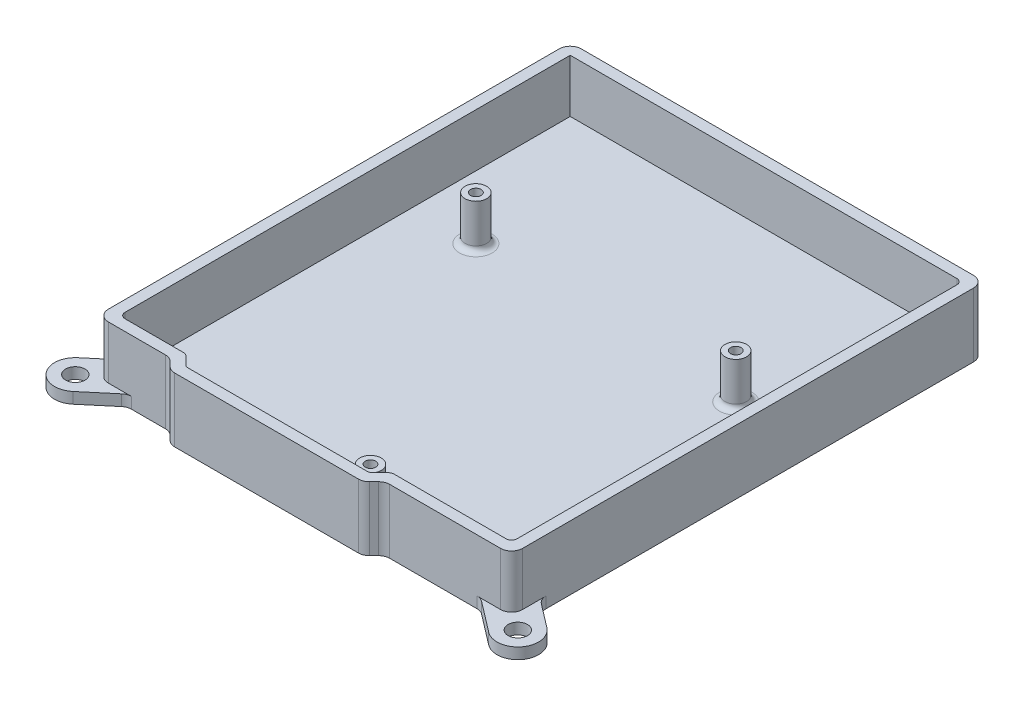
SolidWorks part; units mm, degrees
ref_plane "Alzado" through (0, 0, 0) normal (0, 0, 1) x (1, 0, 0)
ref_plane "Planta" through (0, 0, 0) normal (0, 1, 0) x (1, 0, 0)
ref_plane "Vista lateral" through (0, 0, 0) normal (1, 0, 0) x (0, 0, -1)
sketch "Croquis1" plane through (0, 0, 0) normal (0, 1, 0) x (1, 0, 0)
  line B0 (-18.7249, 81.5) -> (70.898, 81.5)
  line B1 (70.898, 81.5) -> (70.898, 0)
  line B2 (70.898, 0) -> (49.2071, 0)
  line B3 (49.2071, 0) -> (47.2071, -2)
  line B4 (47.2071, -2) -> (14, -2)
  line B5 (14, -2) -> (12, 0)
  line B6 (12, 0) -> (0, 0)
  line B7 (0, 0) -> (0, 55.5)
  line B8 (0, 55.5) -> (-18.7249, 55.5)
  line B9 (-18.7249, 55.5) -> (-18.7249, 81.5)
  circle B10 centre (-16.2249, 78.75) radius 0.95
  circle B11 centre (-16.2249, 58.25) radius 0.95
  circle B12 centre (11.37, 53.07) radius 0.95
  circle B13 centre (59.63, 51.8) radius 0.95
  circle B14 centre (44.39, 1) radius 0.95
  circle B15 centre (75.675, -3.65) radius 1.75
  circle B16 centre (75.675, 86.35) radius 1.75
  circle B17 centre (-24.325, 86.35) radius 1.75
  circle B18 centre (-4.325, -3.65) radius 1.75
sketch_block_instance "Bloque1-1"
sketch_block "Bloque1"
sketch "Croquis2" plane through (0, 0, 0) normal (0, 1, 0) x (1, 0, 0)
  line L0 (-2, -0.7077) -> (-2, 3.2191) construction
  line L1 (-2, 3.2191) -> (-2, 53.5)
  line L2 (-2, -2) -> (-2, 53.5) construction
  line L3 (-2, -1.6879) -> (-2, -0.7077) construction
  line L4 (-2.9876, -2.5213) -> (-2, -1.6879) construction
  line L5 (0, 55.5) -> (0, 83.5)
  line L6 (-2, 53.5) -> (-2, 83.5)
  line L7 (0, 55.5) -> (-18.7249, 55.5) construction
  line L8 (-18.7249, 81.5) -> (70.898, 81.5) construction
  line L16 (70.898, 81.5) -> (70.898, 0) construction
  line L17 (70.898, 0) -> (49.2071, 0) construction
  line L18 (49.2071, 0) -> (47.2071, -2) construction
  line L19 (47.2071, -2) -> (14, -2) construction
  line L20 (14, -2) -> (12, 0) construction
  line L21 (12, 0) -> (0, 0) construction
  line L22 (0, 0) -> (0, 55.5) construction
  line L24 (-18.7249, 81.5) -> (70.898, 81.5) construction
  line L26 (70.898, 81.5) -> (70.898, 0) construction
  line L27 (70.898, 0) -> (49.2071, 0) construction
  line L28 (49.2071, 0) -> (47.2071, -2)
  line L29 (47.2071, -2) -> (14, -2)
  line L30 (14, -2) -> (12, 0)
  line L31 (12, 0) -> (0, 0) construction
  line L32 (0, 0) -> (0, 55.5)
  line L34 (-2, 81.5) -> (70.898, 81.5) construction
  line L36 (-2, 83.5) -> (67.6044, 83.5)
  line L37 (72.898, 78.1866) -> (72.898, 3.1912)
  line L38 (72.898, -2) -> (72.3075, -2) construction
  line L39 (50.0355, -2) -> (48.0355, -4)
  line L40 (48.0355, -4) -> (13.1716, -4)
  line L41 (13.1716, -4) -> (11.1716, -2)
  line L42 (11.1716, -2) -> (3.4445, -2)
  line L43 (-2, -2) -> (-2, -1.6879) construction
  line L49 (-4.325, -3.65) -> (-2.9876, -2.5213) construction
  line L50 (75.675, -3.65) -> (74.2845, -2.5875) construction
  line L51 (70.898, 81.5) -> (72.8679, 83.5) construction
  line L54 (77.9518, -0.6703) -> (72.898, 3.1912)
  line L55 (73.3982, -6.6297) -> (67.339, -2)
  line L56 (-1.9064, -6.5158) -> (3.4445, -2)
  line L57 (-6.7436, -0.7842) -> (-2, 3.2191)
  line L59 (-20.7249, 83.5) -> (72.898, 83.5) construction
  line L63 (-20.7249, 53.5) -> (-20.7249, 83.5) construction
  line L64 (67.6044, 83.5) -> (72.8679, 83.5)
  line L65 (72.8679, 83.5) -> (72.898, 83.5)
  line L68 (72.898, 83.5) -> (72.898, 78.1866)
  line L69 (72.898, 83.5) -> (72.898, -2) construction
  line L70 (72.898, 3.1912) -> (72.898, -1.1299) construction
  line L71 (72.898, -1.5282) -> (72.898, -2) construction
  line L72 (74.2845, -2.5875) -> (72.898, -1.5282) construction
  line L73 (72.898, -1.5282) -> (72.6953, -1.3732) construction
  line L74 (72.3075, -2) -> (67.339, -2) construction
  line L75 (67.339, -2) -> (50.0355, -2)
  line L76 (72.898, -2) -> (50.0355, -2) construction
  line L77 (72.6953, -1.3732) -> (70.898, 0) construction
  line L78 (72.898, -1.1299) -> (72.898, -1.5282) construction
  line L79 (3.4445, -2) -> (-0.9575, -2) construction
  line L80 (-0.9575, -2) -> (-2, -2) construction
  line L81 (11.1716, -2) -> (-2, -2) construction
  line L82 (-2, -1.6879) -> (-1.4592, -1.2314) construction
  line L83 (-1.4592, -1.2314) -> (0, 0) construction
  line L84 (-2, 53.5) -> (-20.7249, 53.5) construction
  line L85 (-18.7249, 55.5) -> (-18.7249, 81.5) construction
  arc A0 (-2, -0.7077) -> (-6.7436, -0.7842) centre (-4.325, -3.65) ccw construction
  circle A5 centre (75.675, -3.65) radius 1.75 construction
  circle A6 centre (-4.325, -3.65) radius 1.75 construction
  circle A9 centre (75.675, -3.65) radius 1.75
  circle A10 centre (-4.325, -3.65) radius 1.75
  arc A13 (-0.9575, -2) -> (-1.4592, -1.2314) centre (-4.325, -3.65) ccw construction
  arc A14 (72.898, -1.1299) -> (72.6953, -1.3732) centre (75.675, -3.65) ccw construction
  arc A22 (77.9518, -0.6703) -> (72.898, -1.1299) centre (75.675, -3.65) ccw construction
  circle A23 centre (75.675, -3.65) radius 3.75 construction
  arc A24 (72.3075, -2) -> (73.3982, -6.6297) centre (75.675, -3.65) ccw construction
  arc A25 (73.3982, -6.6297) -> (77.9518, -0.6703) centre (75.675, -3.65) ccw
  arc A26 (72.6953, -1.3732) -> (72.3075, -2) centre (75.675, -3.65) ccw construction
  arc A27 (-1.9064, -6.5158) -> (-0.9575, -2) centre (-4.325, -3.65) ccw construction
  circle A28 centre (-4.325, -3.65) radius 3.75 construction
  arc A29 (-1.4592, -1.2314) -> (-2, -0.7077) centre (-4.325, -3.65) ccw construction
  arc A30 (-6.7436, -0.7842) -> (-1.9064, -6.5158) centre (-4.325, -3.65) ccw
  dimension "D1" = 2
extrude "Saliente-Extruir1" add sketch "Croquis2" along normal blind 2 contours L57 A30 L56 L42 L41 L40 L39 L75 L55 A25 L54 L37 L36 L1 A9 A10 region at (35.4124, 0, -39.6065)
sketch "Croquis3" plane through (0, 2, 0) normal (0, 1, 0) x (1, 0, 0)
  line L0 (70.898, 81.5) -> (70.898, 0) construction
  line L1 (49.2071, 0) -> (47.2071, -2) construction
  line L2 (70.898, 0) -> (49.2071, 0) construction
  line L3 (12, 0) -> (0, 0) construction
  line L4 (14, -2) -> (12, 0) construction
  line L5 (47.2071, -2) -> (14, -2) construction
  line L6 (0, 0) -> (0, 55.5) construction
  line L8 (-18.7249, 81.5) -> (70.898, 81.5) construction
  line L10 (70.898, 81.5) -> (70.898, 0)
  line L11 (49.2071, 0) -> (47.2071, -2)
  line L12 (70.898, 0) -> (49.2071, 0)
  line L13 (12, 0) -> (0, 0)
  line L14 (14, -2) -> (12, 0)
  line L15 (47.2071, -2) -> (14, -2)
  line L16 (0, 0) -> (0, 55.5)
  line L18 (0, 81.5) -> (70.898, 81.5)
  line L20 (-2, 83.5) -> (72.898, 83.5)
  line L21 (72.898, 83.5) -> (72.898, -2)
  line L22 (72.898, -2) -> (50.0355, -2)
  line L23 (50.0355, -2) -> (48.0355, -4)
  line L24 (48.0355, -4) -> (13.1716, -4)
  line L25 (13.1716, -4) -> (11.1716, -2)
  line L26 (11.1716, -2) -> (-2, -2)
  line L27 (-2, -2) -> (-2, 53.5)
  line L31 (-2, 83.5) -> (-2, 53.5)
  line L32 (0, 55.5) -> (-18.7249, 55.5) construction
  line L33 (-2, 53.5) -> (-20.7249, 53.5) construction
  line L34 (-18.7249, 55.5) -> (-18.7249, 81.5) construction
  line L35 (-20.7249, 53.5) -> (-20.7249, 83.5) construction
  line L36 (-20.7249, 83.5) -> (72.898, 83.5) construction
  line L37 (-18.7249, 81.5) -> (70.898, 81.5) construction
  line L38 (0, 55.5) -> (0, 81.5)
  point P26 (0.4029, 81.5)
  dimension "D1" = 2
extrude "Saliente-Extruir2" add sketch "Croquis3" along normal blind 9.58
sketch "Croquis4" plane through (0, 2, 0) normal (0, 1, 0) x (1, 0, 0)
  circle A0 centre (44.39, 1) radius 0.95 construction
  circle A1 centre (59.63, 51.8) radius 0.95 construction
  circle A2 centre (11.37, 53.07) radius 0.95 construction
  circle A5 centre (44.39, 1) radius 0.95
  circle A6 centre (59.63, 51.8) radius 0.95
  circle A7 centre (11.37, 53.07) radius 0.95
  circle A12 centre (11.37, 53.07) radius 1.95
  circle A13 centre (59.63, 51.8) radius 1.95
  circle A14 centre (44.39, 1) radius 1.95
  dimension "D2" = 1
extrude "Saliente-Extruir3" add sketch "Croquis4" along normal blind 8
fillet "Redondeo8" radius 2 12 edges at (72.898, 6.79, 2) (-2, 1, -3.2191) (-2, 6.79, 2) (3.4445, 1, 2) (11.1716, 5.79, 2) (13.1716, 5.79, 4) (50.0355, 5.79, 2) (48.0355, 5.79, 4) (72.898, 5.79, -83.5) (72.898, 1, -3.1912) (67.339, 1, 2) (-2, 5.79, -83.5)
fillet "Redondeo6" radius 1 7 edges at (70.898, 6.79, -81.5) (70.898, 6.79, 0) (49.2071, 6.79, 0) (47.2071, 6.79, 2) (14, 6.79, 2) (12, 6.79, 0) (0, 6.79, 0)
fillet "Redondeo7" radius 1 3 edges at (44.39, 2, 0.95) (59.63, 2, -49.85) (11.37, 2, -51.12)
